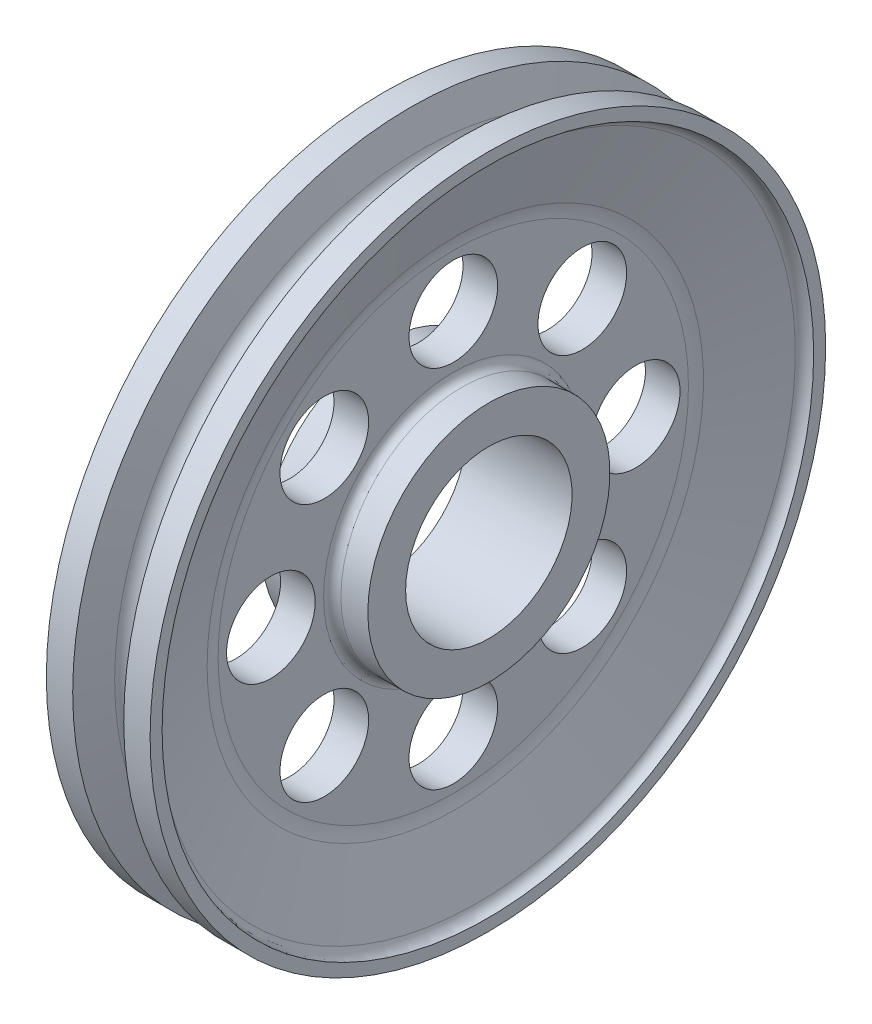
SolidWorks part; units mm, degrees
ref_plane "Piano frontale" through (0, 0, 0) normal (0, 0, 1) x (1, 0, 0)
ref_plane "Piano superiore" through (0, 0, 0) normal (0, 1, 0) x (1, 0, 0)
ref_plane "Piano destro" through (0, 0, 0) normal (1, 0, 0) x (0, 0, -1)
sketch "Sketch1" plane through (0, 0, 0) normal (0, 0, 1) x (1, 0, 0)
  line L0 (-62.2549, -192.8871) -> (72.6149, -192.8871) construction
  line L1 (0, -192.8871) -> (0, 154.8776) construction
  line L2 (35.3511, 156.8497) -> (0, 44.7302) construction
  line L3 (14.3058, 90.1023) -> (23.6104, 119.6129)
  line L4 (23.6104, 119.6129) -> (48, 119.6129)
  line L5 (38.2212, 101.3202) -> (17.8513, 36.7152)
  line L6 (16, 24.687) -> (16, -72.8871)
  line L7 (24, -80.8871) -> (48.9, -80.8871)
  line L8 (48.9, -80.8871) -> (48.9, -115.8871)
  line L9 (48.9, -115.8871) -> (0, -115.8871)
  line L10 (48, 119.6129) -> (48, 108.4903)
  line L11 (0, 79.6129) -> (0, -115.8871)
  circle A0 centre (0, 94.6129) radius 15 construction
  arc A1 (0, 79.6129) -> (14.3058, 90.1023) centre (0, 94.6129) ccw
  arc A3 (48, 108.4903) -> (38.2212, 101.3202) centre (48, 98.237) ccw
  arc A4 (16, -72.8871) -> (24, -80.8871) centre (24, -72.8871) ccw
  arc A5 (16, 24.687) -> (17.8513, 36.7152) centre (56, 24.687) cw
  dimension "D2" = 17.5
  dimension "D3" = 48
  dimension "D4" = 40
  dimension "D5" = 272.5
  dimension "D1" = 30
  dimension "D8" = 8
  dimension "D9" = 40
  dimension "D6" = 77
  dimension "D7" = 16
  dimension "D10" = 35
  dimension "D11" = 48.9
revolve "Puleggia" add sketch "Sketch1" angle 360 about L0
ref_axis "Axis1" through (48.9, -192.8871, 0) along (-1, 0, 0)
mirror "Mirror" about plane through (0, 79.6129, 0) normal (1, 0, 0) of "Puleggia"
sketch "Sketch2" plane through (0, 0, 0) normal (1, 0, 0) x (0, 0, -1)
  line L0 (0, -192.6685) -> (0, -72.8871) construction
  line L1 (0, -72.8871) -> (0, -24.1001) construction
  line L3 (0, -24.1001) -> (0, 24.687) construction
  circle A0 centre (0, -24.1001) radius 41
  circle A1 centre (0, -192.8871) radius 120 construction
  circle A2 centre (0, -192.8871) radius 217.5741 construction
  dimension "D2" = 82
extrude "Foro" cut sketch "Sketch2" against normal blind 120 from offset 60
pattern_circular "PatternFori" count 8 over 360 about axis through (48.9, -192.8871, 0) along (-1, 0, 0) of "Foro"
